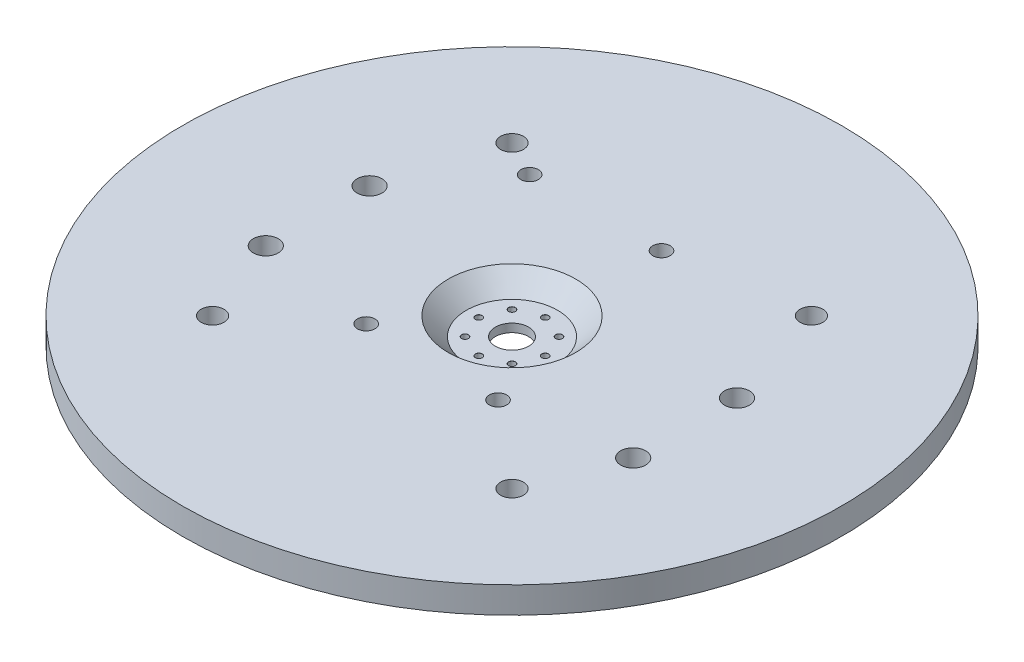
SolidWorks part; units mm, degrees
other "Markup1"
sketch "Sketch21" plane through (-65.5, -15.05, -60) normal (-0.0927, -0.2854, -0.9539) x (0.9951, -0.0609, -0.0785)
material "6061 Alloy"
ref_plane "Front Plane" through (0, 0, 0) normal (0, 0, 1) x (1, 0, 0)
ref_plane "Top Plane" through (0, 0, 0) normal (0, 1, 0) x (1, 0, 0)
ref_plane "Right Plane" through (0, 0, 0) normal (1, 0, 0) x (0, 0, -1)
sketch "Sketch1" plane through (0, 0, 0) normal (0, 1, 0) x (1, 0, 0)
  circle A0 centre (0, 0) radius 79.375
  dimension "D1" = 158.75
extrude "Boss-Extrude1" add sketch "Sketch1" along normal mid plane 6.35
sketch "Sketch2" plane through (0, -3.175, 0) normal (0, -1, 0) x (1, 0, 0)
  circle A0 centre (0, 0) radius 12.065
  circle A1 centre (0, 0) radius 79.375 construction
  dimension "D1" = 24.13
sketch "Sketch5" plane through (0, 3.175, 0) normal (0, 1, 0) x (1, 0, 0)
  circle A0 centre (0, 0) radius 10.4
  circle A1 centre (0, 0) radius 79.375 construction
  dimension "D1" = 20.8
hole_wizard "Tap Drill for M5x0.8 Tap1" positions "Sketch22" profile "Sketch23" hole size "M5x0.8" standard "ANSI Metric" end condition through all
sketch "Sketch22" plane through (0, 3.175, 0) normal (0, 1, 0) x (1, 0, 0)
  point P0 (-27.3188, 31.5712)
  point P3 (4.4312, 31.5712)
  point P6 (-15.875, -19.2459)
  point P9 (15.875, -19.2459)
  dimension "D1" = 31.75
  dimension "D2" = 31.5712
  dimension "D3" = 4.4312
  dimension "D4" = 31.75
  dimension "D5" = 19.2459
  dimension "D6" = 15.875
sketch "Sketch23" plane through (-27.3188, 3.175, -31.5712) normal (1, 0, 0) x (0, 0, 1)
  line L0 (0, 0) -> (0, 6.35)
  line L1 (0, 6.35) -> (2.1, 6.35)
  line L2 (2.1, 6.35) -> (2.1, 0)
  line L5 (2.1, 0) -> (0, 0)
  line L11 (0, -6.35) -> (0, 107.95) construction
  dimension "Thru Hole Dia." = 4.2
  dimension "Thru Hole Depth" = 6.35
hole_wizard "Tap Drill for M7x1.0 Tap1" positions "Sketch24" profile "Sketch25" hole size "M7x1.0" standard "ANSI Metric" end condition through all
sketch "Sketch24" plane through (0, 3.175, 0) normal (0, 1, 0) x (1, 0, 0)
  point P0 (-44.245, 9.9416)
  point P3 (-44.245, -15.0584)
  point P6 (44.245, 9.9416)
  point P9 (44.245, -15.0584)
  dimension "D1" = 25
  dimension "D2" = 44.245
  dimension "D3" = 9.9416
  dimension "D4" = 25
  dimension "D5" = 44.245
  dimension "D6" = 15.0584
sketch "Sketch25" plane through (-44.245, 3.175, -9.9416) normal (1, 0, 0) x (0, 0, 1)
  line L0 (0, 0) -> (0, 6.35)
  line L1 (0, 6.35) -> (3, 6.35)
  line L2 (3, 6.35) -> (3, 0)
  line L5 (3, 0) -> (0, 0)
  line L11 (0, -6.35) -> (0, 107.95) construction
  dimension "Thru Hole Dia." = 6
  dimension "Thru Hole Depth" = 6.35
sketch "Sketch28" plane through (0, 3.175, 0) normal (0, 1, 0) x (1, 0, 0)
  circle A0 centre (0, 0) radius 51
  circle A1 centre (35.8572, -36.2665) radius 4.2952
  dimension "D1" = 102
hole_wizard "M5 Clearance Hole1" positions "Sketch29" profile "Sketch30" hole size "M5" standard "ANSI Metric" end condition through all
sketch "Sketch29" plane through (0, 3.175, 0) normal (0, 1, 0) x (1, 0, 0)
  line L0 (-36.0624, 36.0624) -> (-36.0624, -36.0624) construction
  line L2 (-36.0624, 36.0624) -> (36.0624, 36.0624) construction
  line L3 (36.0624, 36.0624) -> (36.0624, -36.0624) construction
  line L4 (36.0624, -36.0624) -> (-36.0624, -36.0624) construction
  circle A0 centre (0, 0) radius 51 construction
  point P0 (-36.0624, 36.0624)
  point P4 (-36.0624, -36.0624)
  point P6 (36.0624, -36.0624)
  point P8 (36.0624, 36.0624)
sketch "Sketch30" plane through (-36.0624, 3.175, -36.0624) normal (1, 0, 0) x (0, 0, 1)
  line L0 (0, 0) -> (0, 6.35)
  line L1 (0, 6.35) -> (2.75, 6.35)
  line L2 (2.75, 6.35) -> (2.75, 0)
  line L5 (2.75, 0) -> (0, 0)
  line L11 (0, -6.35) -> (0, 107.95) construction
  dimension "Thru Hole Dia." = 5.5
  dimension "Thru Hole Depth" = 6.35
sketch "Sketch31" plane through (0, 3.175, 0) normal (0, 1, 0) x (1, 0, 0)
  line L1 (5.6569, 5.6569) -> (-5.6569, 5.6569) construction
  line L2 (5.6569, 5.6569) -> (5.6569, -5.6569) construction
  line L3 (5.6569, -5.6569) -> (-5.6569, -5.6569) construction
  line L4 (-5.6569, 5.6569) -> (-5.6569, -5.6569) construction
  line L5 (5.6569, 5.6569) -> (-5.6569, -5.6569) construction
  line L6 (5.6569, -5.6569) -> (-5.6569, 5.6569) construction
  line L7 (8, 0) -> (0, 8) construction
  line L8 (8, 0) -> (0, -8) construction
  line L9 (0, -8) -> (-8, 0) construction
  line L10 (0, 8) -> (-8, 0) construction
  line L11 (8, 0) -> (-8, 0) construction
  line L12 (0, -8) -> (0, 8) construction
  circle A0 centre (0, 0) radius 8 construction
  point P0 (0, 0)
  point P8 (0, 0)
  point P13 (0, 0)
  point P14 (-0.9641, 7.9417)
  point P15 (-7.7325, 2.0514)
  point P16 (7.9463, -0.9255)
  point P17 (0, -8)
  dimension "D1" = 16
sketch "Sketch32" plane through (0, 3.175, 0) normal (0, 1, 0) x (1, 0, 0)
  circle A0 centre (0, 0) radius 11
  circle A1 centre (0, 0) radius 4
  dimension "D1" = 22
  dimension "D2" = 8
extrude "Cut-Extrude1" cut sketch "Sketch32" against normal through all contours A1
extrude "Cut-Extrude2" cut sketch "Sketch32<4>" against normal offset from surface (4.35 mm away) 2 up to face at (0, -3.175, 4)
sketch "Sketch32<4>" plane through (0, 3.175, 0) normal (0, 1, 0) x (1, 0, 0) same geometry as "Sketch32"
chamfer "Chamfer1" distance 4.35 angle 45 1 edges at (0, 3.175, 11)
hole_wizard "Tap Drill for M2x0.4 Tap1" positions "Sketch33" profile "Sketch34" hole size "M2x0.4" standard "ANSI Metric" end condition through all
sketch "Sketch33" plane through (0, -1.175, 0) normal (0, 1, 0) x (1, 0, 0)
  point P0 (-8, 0)
  point P3 (-5.6569, 5.6569)
  point P6 (0, 8)
  point P9 (5.6569, 5.6569)
  point P12 (8, 0)
  point P15 (5.6569, -5.6569)
  point P18 (0, -8)
  point P21 (-5.6569, -5.6569)
sketch "Sketch34" plane through (-8, -1.175, 0) normal (1, 0, 0) x (0, 0, 1)
  line L0 (0, 0) -> (0, 2)
  line L1 (0, 2) -> (0.8, 2)
  line L2 (0.8, 2) -> (0.8, 0.025)
  line L3 (0.8, 0.025) -> (0.825, 0)
  line L5 (0.825, 0) -> (0, 0)
  line L6 (-0.8, 0.025) -> (-0.825, 0) construction
  line L11 (0, -6.35) -> (0, 107.95) construction
  dimension "Thru Hole Dia." = 1.6
  dimension "Thru Hole Depth" = 2
  dimension "Near C'Sink Dia." = 1.65
  dimension "Near C'Sink Angle" = 90
